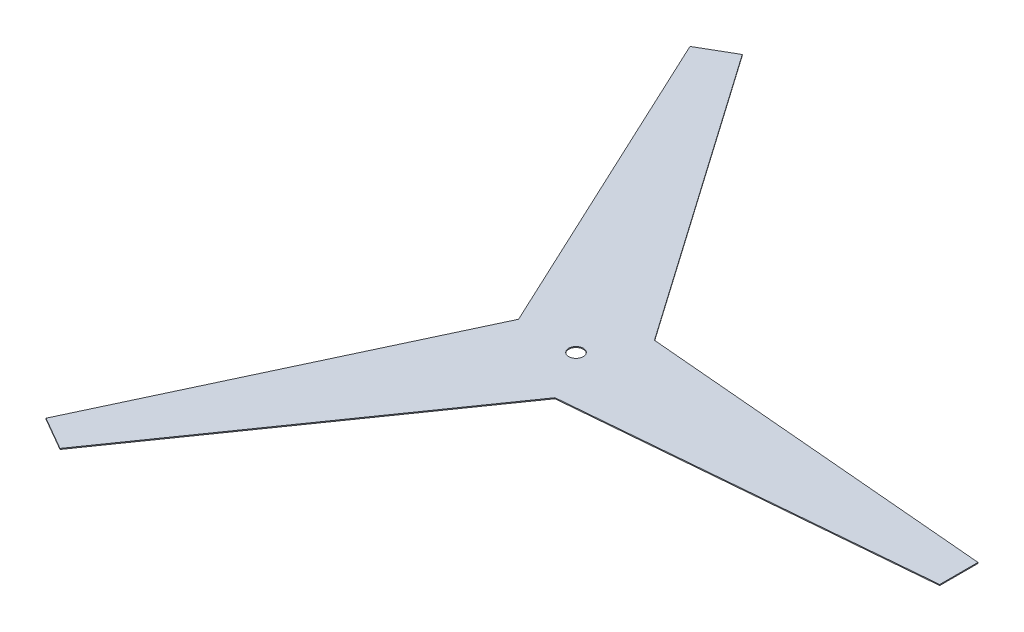
SolidWorks part; units mm, degrees
ref_plane "Alzado" through (0, 0, 0) normal (0, 0, 1) x (1, 0, 0)
ref_plane "Planta" through (0, 0, 0) normal (0, 1, 0) x (1, 0, 0)
ref_plane "Vista lateral" through (0, 0, 0) normal (1, 0, 0) x (0, 0, -1)
sketch "Croquis1" plane through (0, 0, 0) normal (0, 1, 0) x (1, 0, 0)
  line L0 (0, 0) -> (1000, 0) construction
  line L1 (0, 0) -> (-500, 866.0254) construction
  line L2 (0, 0) -> (-9.525, -16.4978) construction
  line L3 (-500, -866.0254) -> (-554.6259, -923.9835) construction
  line L4 (-456.6987, -891.0254) -> (-543.3013, -841.0254)
  line L6 (1000, 50) -> (1000, -50)
  line L8 (0, 19.05) -> (0, -19.05)
  line L9 (1000, 50) -> (27.2918, -47.2708) construction
  line L10 (1000, -50) -> (500, 0) construction
  line L12 (16.4978, -9.525) -> (-16.4978, 9.525)
  line L14 (-543.3013, 841.0254) -> (-456.6987, 891.0254)
  line L16 (-16.4978, -9.525) -> (16.4978, 9.525)
  line L18 (0, 0) -> (75, -129.9038) construction
  line L19 (0, 0) -> (-19.05, 0) construction
  line L20 (0, 0) -> (9.525, 16.4978) construction
  line L21 (-456.6987, -891.0254) -> (75, -129.9038)
  line L22 (75, -129.9038) -> (1000, -50)
  line L23 (-543.3013, -841.0254) -> (-150, 0)
  line L24 (-150, 0) -> (-543.3013, 841.0254)
  line L25 (1000, 50) -> (75, 129.9038)
  line L26 (75, 129.9038) -> (-456.6987, 891.0254)
  circle A0 centre (0, 0) radius 19.05
  point P3 (500, 0)
  point P23 (0, 0)
  dimension "D14" = 38.1
  dimension "D1" = 1000
  dimension "D2" = 1000
  dimension "D3" = 1000
  dimension "D4" = 120
  dimension "D5" = 120
  dimension "D6" = 100
  dimension "D8" = 60
  dimension "D9" = 60
  dimension "D10" = 60
  dimension "D11" = 150
  dimension "D12" = 150
  dimension "D13" = 150
  dimension "D7" = 3
extrude "Saliente-Extruir3" add sketch "Croquis1" along normal blind 2.5 contours L25 L26 L14 L24 L23 L4 L21 L22 L6 A0 region at (-488.2128, 0, 845.6094)
